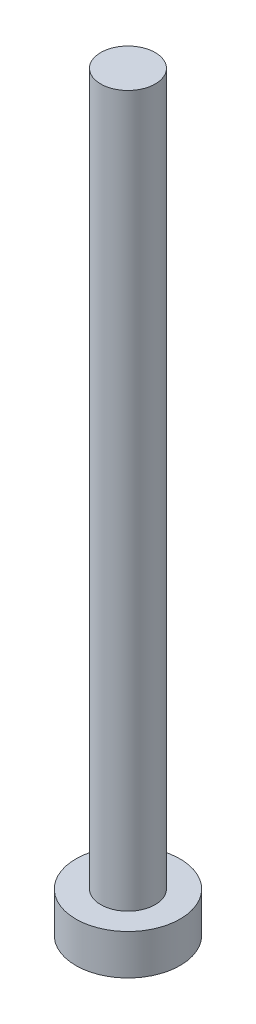
SolidWorks part; units mm, degrees
ref_plane "前视基准面" through (0, 0, 0) normal (0, 0, 1) x (1, 0, 0)
ref_plane "上视基准面" through (0, 0, 0) normal (0, 1, 0) x (1, 0, 0)
ref_plane "右视基准面" through (0, 0, 0) normal (1, 0, 0) x (0, 0, -1)
other "Configuration Table"
sketch "草图1" plane through (0, 0, 0) normal (0, 1, 0) x (1, 0, 0)
  line L7 (-0.85, -0.25) -> (0.85, -0.25)
  line L8 (-0.85, -0.25) -> (-0.85, 0.25)
  line L9 (-0.85, 0.25) -> (0.85, 0.25)
  line L10 (0.85, -0.25) -> (0.85, 0.25)
  line L11 (-0.85, -0.25) -> (0.85, 0.25) construction
  line L12 (-0.85, 0.25) -> (0.85, -0.25) construction
  line L13 (-0.25, -0.85) -> (0.25, -0.85)
  line L14 (-0.25, -0.85) -> (-0.25, 0.85)
  line L15 (-0.25, 0.85) -> (0.25, 0.85)
  line L16 (0.25, -0.85) -> (0.25, 0.85)
  line L17 (-0.25, -0.85) -> (0.25, 0.85) construction
  line L18 (-0.25, 0.85) -> (0.25, -0.85) construction
  circle A1 centre (0, 0) radius 2.2
  circle A2 centre (0, 0) radius 1.15
  dimension "D1" = 1.7
  dimension "D2" = 4.4
  dimension "D3" = 2.3
  dimension "D4" = 0.5
extrude "凸台-拉伸1" add sketch "草图1" along normal blind 1.7 contours A1
extrude "凸台-拉伸2" add sketch "草图1<4>" along normal blind 30 from surface contours A2 starting at face at (0, 1.7, 2.2)
sketch "草图1<4>" plane through (0, 0, 0) normal (0, 1, 0) x (1, 0, 0) same geometry as "草图1"
extrude "切除-拉伸1" cut sketch "草图1<3>" along normal blind 1.5 contours L13 L16 L15 L14 | L7 L10 L9 L8
sketch "草图1<3>" plane through (0, 0, 0) normal (0, 1, 0) x (1, 0, 0) same geometry as "草图1"
